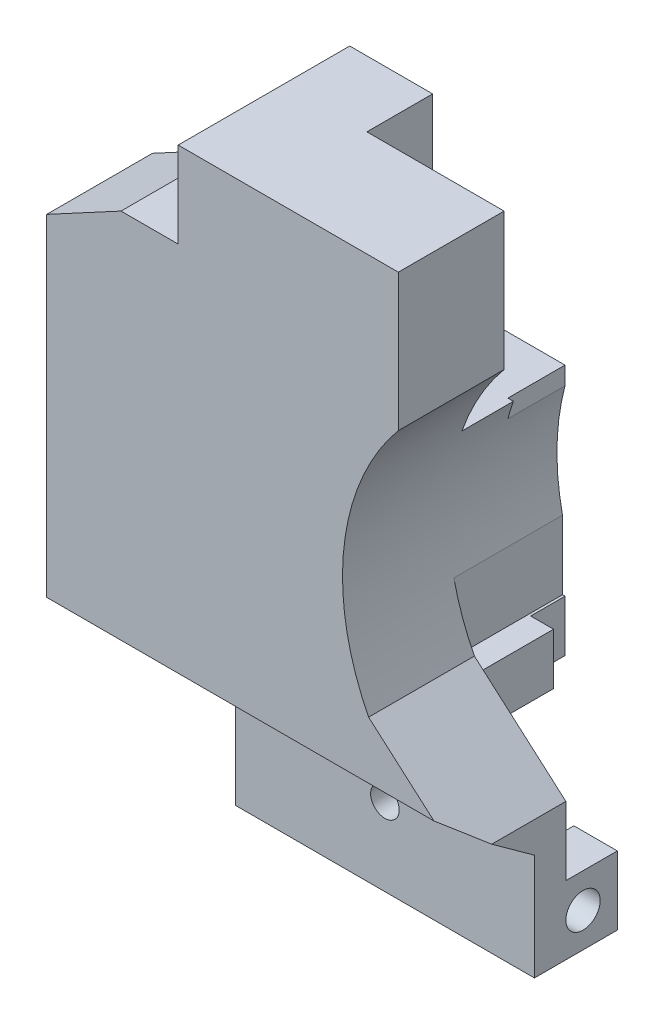
SolidWorks part; units mm, degrees
ref_plane "Front Plane" through (0, 0, 0) normal (0, 0, 1) x (1, 0, 0)
ref_plane "Top Plane" through (0, 0, 0) normal (0, 1, 0) x (1, 0, 0)
ref_plane "Right Plane" through (0, 0, 0) normal (1, 0, 0) x (0, 0, -1)
sketch "Sketch1" plane through (0, 0, 0) normal (0, 0, 1) x (1, 0, 0)
  line L2 (11.5, 3.5) -> (11.5, 11)
  line L3 (11.5, 11) -> (30.75, 11)
  line L4 (30.75, 11) -> (30.75, -1)
  line L8 (36.15, -31) -> (36.15, -43)
  line L10 (36.15, -43) -> (10, -43)
  line L11 (10, -43) -> (10, -34.5)
  line L12 (5, -30.5) -> (0, -30.5)
  line L13 (0, 0) -> (0, -30.5)
  line L15 (11.5, 3.5) -> (6.5, 3.5)
  line L16 (6.5, 3.5) -> (0, 0)
  line L17 (10, -34.5) -> (5, -30.5)
  line L18 (36.15, -31) -> (28.15, -24)
  arc A0 (30.75, -1) -> (28.15, -24) centre (46.9039, -14.473) ccw
  dimension "D13" = 12
  dimension "D1" = 54
  dimension "D3" = 5
  dimension "D4" = 19.25
  dimension "D5" = 6.5
  dimension "D6" = 12
  dimension "D7" = 26.15
  dimension "D8" = 30.5
  dimension "D9" = 10
  dimension "D10" = 7.5
  dimension "D11" = 8.5
  dimension "D12" = 4
  dimension "D15" = 7
extrude "Boss-Extrude1" add sketch "Sketch1" along normal blind 18.75
sketch "Sketch2" plane through (0, 0, 0) normal (0, 0, -1) x (-1, 0, 0)
  point P5 (-18.075, -16)
sketch "Sketch4" plane through (0, 0, 0) normal (0, 0, -1) x (-1, 0, 0)
  line L0 (0, 0) -> (0, -30.5) construction
  line L1 (-36.15, -43) -> (0, -43)
  line L2 (-36.15, -43) -> (-36.15, -30.5)
  line L3 (-36.15, -30.5) -> (0, -30.5)
  line L4 (0, -43) -> (0, -30.5)
  line L5 (0, -30.5) -> (-5, -30.5) construction
extrude "Cut-Extrude1" cut sketch "Sketch4" against normal blind 5
sketch "Sketch5" plane through (0, 0, 5) normal (0, 0, -1) x (-1, 0, 0)
  line L0 (-36.15, -43) -> (-10, -43) construction
  line L1 (-32.35, -43) -> (-13.8, -43)
  line L2 (-32.35, -43) -> (-32.35, -37)
  line L4 (-13.8, -43) -> (-13.8, -37)
  line L5 (-36.15, -31) -> (-36.15, -43) construction
  line L7 (-10, -34.5) -> (-10, -43) construction
  line L9 (-36.15, -37) -> (-32.35, -37)
  line L10 (-36.15, -37) -> (-36.15, -29.5)
  line L11 (-36.15, -29.5) -> (0.9021, -29.5)
  line L12 (0.9021, -37) -> (0.9021, -29.5)
  line L13 (-13.8, -37) -> (0.9021, -37)
  dimension "D1" = 3.8
  dimension "D2" = 3.8
  dimension "D3" = 6
  dimension "D4" = 7.5
extrude "Cut-Extrude2" cut sketch "Sketch5" against normal blind 4.5 and the other way blind 6
sketch "Sketch6" plane through (36.15, 0, 0) normal (1, 0, 0) x (0, 0, -1)
  line L0 (-5, -37) -> (-5, -43) construction
  circle A0 centre (-8, -40) radius 1.5
  dimension "D1" = 3
  dimension "D2" = 3
extrude "Cut-Extrude3" cut sketch "Sketch6" against normal through all
sketch "Sketch7" plane through (0, 0, 0) normal (0, 0, -1) x (-1, 0, 0)
  line L1 (-26.575, -29.5) -> (-9.575, -29.5)
  line L2 (-26.575, -29.5) -> (-26.575, -7.5)
  line L3 (-26.575, -7.5) -> (-9.575, -7.5)
  line L4 (-9.575, -29.5) -> (-9.575, -7.5)
  line L5 (-26.575, -29.5) -> (-9.575, -7.5) construction
  line L6 (-26.575, -7.5) -> (-9.575, -29.5) construction
  line L8 (0, -29.5) -> (-34.4357, -29.5) construction
  line L9 (-28.575, -25) -> (-26.575, -25)
  line L10 (-28.575, -29.5) -> (-8.325, -29.5)
  line L11 (-28.575, -29.5) -> (-28.575, -25)
  line L12 (-28.575, -7.5) -> (-8.325, -7.5)
  line L13 (-8.325, -29.5) -> (-8.325, -25)
  line L14 (-9.575, -25) -> (-8.325, -25)
  line L15 (-28.575, -10) -> (-26.575, -10)
  line L16 (-9.575, -10) -> (-8.325, -10)
  line L17 (-28.575, -10) -> (-28.575, -7.5)
  line L18 (-8.325, -10) -> (-8.325, -7.5)
  point P0 (-18.075, -16)
  arc M21 (-30.75, -1) -> (-28.15, -24) centre (-46.9039, -14.473) cw
  dimension "D1" = 17
  dimension "D2" = 2
  dimension "D3" = 1.25
  dimension "D4" = 4.5
  dimension "D5" = 4.5
  dimension "D6" = 2.5
  dimension "D7" = 2.5
extrude "Cut-Extrude4" cut sketch "Sketch7" against normal blind 3 contours L11 L2 L9 | L14 L4 L13 region at (27.575, -27.25, 0) region at (8.95, -27.25, 0)
extrude "Cut-Extrude5" cut sketch "Sketch7<3>" against normal blind 5 contours L16 L18 L12 L4 | L15 L2 L12 M21 region at (8.95, -8.75, 0) region at (26.7325, -8.0103, 0)
sketch "Sketch7<3>" plane through (0, 0, 0) normal (0, 0, -1) x (-1, 0, 0) same geometry as "Sketch7"
sketch "Sketch8" plane through (0, 0, 0) normal (0, 0, -1) x (-1, 0, 0)
  line L0 (-8.325, -10) -> (-8.325, -7.5)
  line L1 (-8.325, -30.5) -> (0, -30.5)
  line L2 (-8.325, -30.5) -> (-8.325, -25)
  line L5 (-9.575, -25) -> (-8.325, -25)
  line L6 (-9.575, -25) -> (-9.575, -10)
  line L7 (-9.575, -10) -> (-8.325, -10)
  line L9 (-8.325, -7.5) -> (-33.6299, -7.5)
  line L11 (0, 11) -> (-33.6299, 11)
  line L12 (-33.6299, -7.5) -> (-33.6299, 11)
  line L14 (-9.575, -7.5) -> (-8.325, -7.5) construction
  line L15 (0, -30.5) -> (0, 11)
  line L16 (-30.75, 11) -> (-11.5, 11) construction
extrude "Cut-Extrude6" cut sketch "Sketch8" against normal up to surface (9.5 mm away) up to face at (19.299, -35.6786, 9.5)
sketch "Sketch9" plane through (0, 0, 9.5) normal (0, 0, -1) x (-1, 0, 0)
  line L0 (-11.5, 11) -> (-30.75, 11) construction
  line L1 (-18.75, 11) -> (-11.5, 11)
  line L2 (-18.75, 11) -> (-18.75, 4.75)
  line L3 (-18.75, 4.75) -> (-11.5, 4.75)
  line L4 (-11.5, 11) -> (-11.5, 4.75)
  line L5 (-30.75, -1) -> (-30.75, 11) construction
  line L6 (-11.5, 11) -> (-11.5, 3.5) construction
  dimension "D1" = 12
  dimension "D2" = 6.25
extrude "Boss-Extrude2" add sketch "Sketch9" along normal blind 5.75
sketch "Sketch10" plane through (0, 0, 0) normal (0, 0, -1) x (-1, 0, 0)
  line L0 (-28.575, -29.5) -> (-34.4357, -29.5) construction
  line L1 (-35.5786, -29.5) -> (-28.575, -29.5)
  line L2 (-35.5786, -29.5) -> (-35.5786, -22.5672)
  line L3 (-35.5786, -22.5672) -> (-27.4886, -22.5672)
  line L4 (-28.575, -29.5) -> (-28.575, -25)
  line L5 (-28.575, -25) -> (-26.3561, -25)
  line L6 (-27.4886, -22.5672) -> (-27.4886, -9.972)
  line L7 (-27.4886, -9.972) -> (-26.3561, -9.972)
  line L8 (-26.3561, -25) -> (-26.3561, -9.972)
  arc A0 (-28.15, -24) -> (-26.575, -9.0686) centre (-46.9039, -14.473) ccw construction
  arc A2 (-28.15, -24) -> (-26.575, -9.0686) centre (-46.9039, -14.473) ccw construction
extrude "Cut-Extrude7" cut sketch "Sketch10" against normal up to surface (9.5 mm away) up to face at (17.068, -19.5298, 9.5)
sketch "Sketch11" plane through (10, 0, 0) normal (-1, 0, 0) x (0, 0, 1)
  line L0 (18.75, -43) -> (5, -43) construction
  line L1 (12.25, -43) -> (18.75, -43)
  line L2 (12.25, -43) -> (12.25, -33.7)
  line L5 (18.75, -43) -> (18.75, -29)
  line L6 (5, -37) -> (5, -43) construction
  line L7 (12.25, -33.7) -> (18.75, -29)
  dimension "D1" = 7.25
  dimension "D2" = 9.3
  dimension "D3" = 14
extrude "Cut-Extrude8" cut sketch "Sketch11" against normal through all and the other way blind 12
sketch "Sketch12" plane through (0, 0, 12.25) normal (0, 0, 1) x (1, 0, 0)
  line L0 (9, -33.7) -> (36.15, -33.7) construction
  line L1 (27.15, -33.7) -> (12, -33.7)
  line L2 (27.15, -33.7) -> (27.15, -29)
  line L3 (27.15, -29) -> (12, -29)
  line L4 (12, -33.7) -> (12, -29)
  line L5 (0, -29) -> (33.8643, -29) construction
  line L6 (10, -34.5) -> (10, -43) construction
  line L7 (36.15, -31) -> (36.15, -33.7) construction
  dimension "D1" = 2
  dimension "D2" = 9
extrude "Cut-Extrude11" cut sketch "Sketch12" along normal blind 6 and the other way up to surface (2.75 mm away) other way up to face at (18.1662, -19.9958, 9.5)
sketch "Sketch13" plane through (0, 0, 12.25) normal (0, 0, 1) x (1, 0, 0)
  line L1 (36.15, -33.7) -> (36.15, -43) construction
  line L2 (12, -33.7) -> (27.15, -33.7) construction
  circle A0 centre (23.075, -36.2) radius 1.25
  dimension "D2" = 2.5
  dimension "D1" = 13.075
  dimension "D3" = 2.5
extrude "Cut-Extrude12" cut sketch "Sketch13" against normal through all
